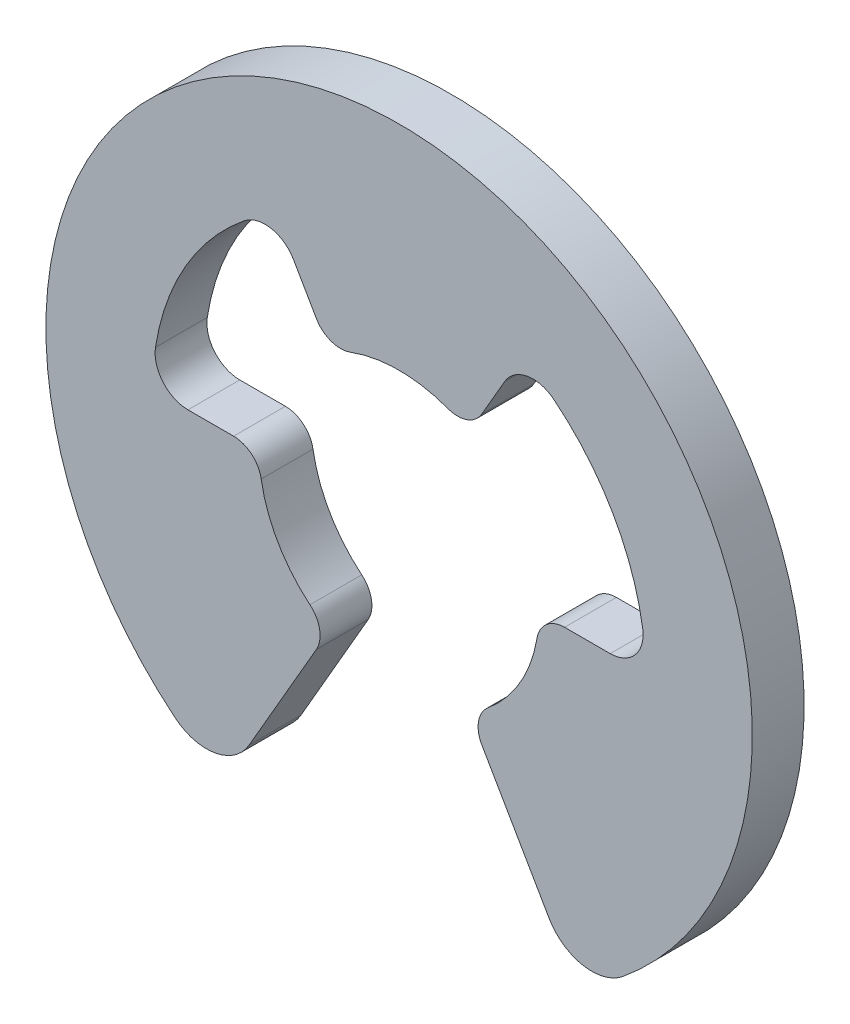
SolidWorks part; units mm, degrees
material "Plain Carbon Steel"
ref_plane "Front Plane" through (0, 0, 0) normal (0, 0, 1) x (1, 0, 0)
ref_plane "Top Plane" through (0, 0, 0) normal (0, 1, 0) x (1, 0, 0)
ref_plane "Right Plane" through (0, 0, 0) normal (1, 0, 0) x (0, 0, -1)
sketch "Sketch1" plane through (0, 0, 0) normal (0, 0, 1) x (1, 0, 0)
  line L0 (-2.0217, -3.5017) -> (-1.1157, -1.9325)
  line L1 (-2.2315, 0) -> (-2.8467, 0)
  line L2 (-1.4233, 2.4653) -> (-1.1157, 1.9325)
  line L3 (1.1157, 1.9325) -> (1.4233, 2.4653)
  line L4 (2.8467, 0) -> (2.2315, 0)
  line L5 (1.1157, -1.9325) -> (2.0217, -3.5017)
  arc A0 (3.0189, -3.6834) -> (-3.0189, -3.6834) centre (0, 0) ccw
  arc A1 (-3.0189, -3.6834) -> (-2.0217, -3.5017) centre (-2.5975, -3.1692) ccw
  arc A2 (-1.1157, -1.9325) -> (-1.202, -1.4533) centre (-1.4424, -1.7439) ccw
  arc A3 (-1.202, -1.4533) -> (-1.8596, -0.3143) centre (0, 0) cw
  arc A4 (-1.8596, -0.3143) -> (-2.2315, 0) centre (-2.2315, -0.3772) ccw
  arc A5 (-2.8467, 0) -> (-3.2846, 0.5114) centre (-2.8467, 0.4432) cw
  arc A6 (-3.2846, 0.5114) -> (-2.0852, 2.5889) centre (0, 0) cw
  arc A7 (-2.0852, 2.5889) -> (-1.4233, 2.4653) centre (-1.8072, 2.2437) cw
  arc A8 (-1.1157, 1.9325) -> (-0.6576, 1.7676) centre (-0.7891, 2.1211) ccw
  arc A9 (-0.6576, 1.7676) -> (0.6576, 1.7676) centre (0, 0) cw
  arc A10 (0.6576, 1.7676) -> (1.1157, 1.9325) centre (0.7891, 2.1211) ccw
  arc A11 (1.4233, 2.4653) -> (2.0852, 2.5889) centre (1.8072, 2.2437) cw
  arc A12 (2.0852, 2.5889) -> (3.2846, 0.5114) centre (0, 0) cw
  arc A13 (3.2846, 0.5114) -> (2.8467, 0) centre (2.8467, 0.4432) cw
  arc A14 (2.2315, 0) -> (1.8596, -0.3143) centre (2.2315, -0.3772) ccw
  arc A15 (1.8596, -0.3143) -> (1.202, -1.4533) centre (0, 0) cw
  arc A16 (1.202, -1.4533) -> (1.1157, -1.9325) centre (1.4424, -1.7439) ccw
  arc A17 (2.0217, -3.5017) -> (3.0189, -3.6834) centre (2.5975, -3.1692) ccw
extrude "Boss-Extrude1" add sketch "Sketch1" against normal blind 0.3493 and the other way blind 0.3493
ref_plane "RR XY" through (0, 0, 0) normal (0, 0, 1) x (1, 0, 0)
ref_plane "RR XZ" through (0, 0, 0) normal (0, -1, 0) x (-1, 0, 0)
ref_plane "RR YZ" through (0, 0, 0) normal (1, 0, 0) x (0, 0, -1)
ref_axis "RR X" through (-80.9, 0, 0) along (1, 0, 0)
ref_axis "RR Y" through (0, -50, 0) along (0, 1, 0)
ref_axis "RR Z" through (0, 0, 80.9) along (0, 0, -1)
sketch3d "RR"
  point P0 (0, 0, 0)
